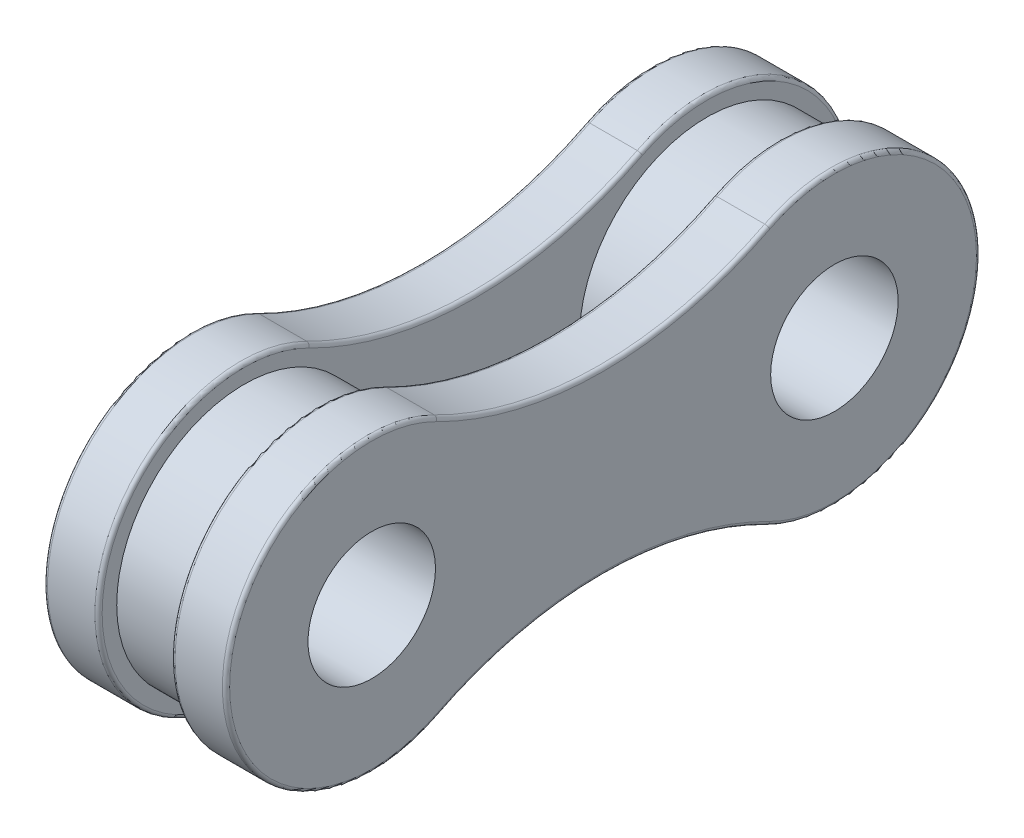
SolidWorks part; units mm, degrees
ref_plane "Front Plane" through (0, 0, 0) normal (0, 0, 1) x (1, 0, 0)
ref_plane "Top Plane" through (0, 0, 0) normal (0, 1, 0) x (1, 0, 0)
ref_plane "Right Plane" through (0, 0, 0) normal (1, 0, 0) x (0, 0, -1)
sketch "Sketch1" plane through (0, 0, 0) normal (1, 0, 0) x (0, 0, -1)
  line L0 (6.35, 0) -> (-6.35, 0) construction
  line L1 (0, -12265.2787) -> (0, 12284.0066) construction
  arc A0 (-4.5357, 3.5649) -> (-4.5357, -3.5649) centre (-6.35, 0) ccw
  circle A1 centre (-6.35, 0) radius 1.75
  circle A2 centre (6.35, 0) radius 1.75
  arc A3 (4.5357, 3.5649) -> (4.5357, -3.5649) centre (6.35, 0) cw
  arc A4 (-4.5357, 3.5649) -> (4.5357, 3.5649) centre (0, 12.4771) ccw
  arc A5 (-4.5357, -3.5649) -> (4.5357, -3.5649) centre (0, -12.4771) cw
  dimension "D2" = 8
  dimension "D3" = 3.5
  dimension "D4" = 10
  dimension "D1" = 12.7
extrude "Boss-Extrude1" add sketch "Sketch1" along normal blind 1.5 from offset 1
sketch "Sketch2" plane through (0, 0, 0) normal (1, 0, 0) x (0, 0, -1)
  circle A0 centre (-6.35, 0) radius 1.75 construction
  circle A1 centre (6.35, 0) radius 1.75 construction
  circle A2 centre (-6.35, 0) radius 1.75
  circle A3 centre (6.35, 0) radius 1.75
  arc A4 (4.5357, -3.5649) -> (-4.5357, -3.5649) centre (0, -12.4771) ccw
  arc A5 (4.5357, -3.5649) -> (4.5357, 3.5649) centre (6.35, 0) ccw
  arc A6 (-4.5357, 3.5649) -> (4.5357, 3.5649) centre (0, 12.4771) ccw
  arc A7 (-4.5357, 3.5649) -> (-4.5357, -3.5649) centre (-6.35, 0) ccw
  arc A8 (4.5357, -3.5649) -> (-4.5357, -3.5649) centre (0, -12.4771) ccw
  arc A9 (4.5357, -3.5649) -> (4.5357, 3.5649) centre (6.35, 0) ccw
  arc A10 (-4.5357, 3.5649) -> (4.5357, 3.5649) centre (0, 12.4771) ccw
  arc A11 (-4.5357, 3.5649) -> (-4.5357, -3.5649) centre (-6.35, 0) ccw
  dimension "D1" = 0
extrude "Boss-Extrude2" add sketch "Sketch2" against normal blind 1.5 from offset 1 separate body offset against normal yes
sketch "Sketch3" plane through (0, 0, 0) normal (1, 0, 0) x (0, 0, -1)
  line L0 (0, -1146.9345) -> (0, 5479.7981) construction
  circle A0 centre (6.35, 0) radius 1.75 construction
  circle A1 centre (-6.35, 0) radius 1.75 construction
  circle A2 centre (6.35, 0) radius 1.75
  circle A3 centre (-6.35, 0) radius 1.75
  circle A4 centre (6.35, 0) radius 3.5
  circle A5 centre (-6.35, 0) radius 3.5
  dimension "D1" = 7
extrude "Boss-Extrude3" add sketch "Sketch3" along normal mid plane 2
fillet "Fillet1" radius 0.1 16 edges at (2.5, 0, 10.35) (2.5, 2.4771, 0) (2.5, 0, -10.35) (1, 0, 10.35) (1, 2.4771, 0) (1, 0, -10.35) (-1, 0, 10.35) (-1, 2.4771, 0) (-1, 0, -10.35) (-2.5, 0, 10.35) (-2.5, 2.4771, 0) (-2.5, 0, -10.35) (2.5, -2.4771, 0) (1, -2.4771, 0) (-1, -2.4771, 0) (-2.5, -2.4771, 0)
